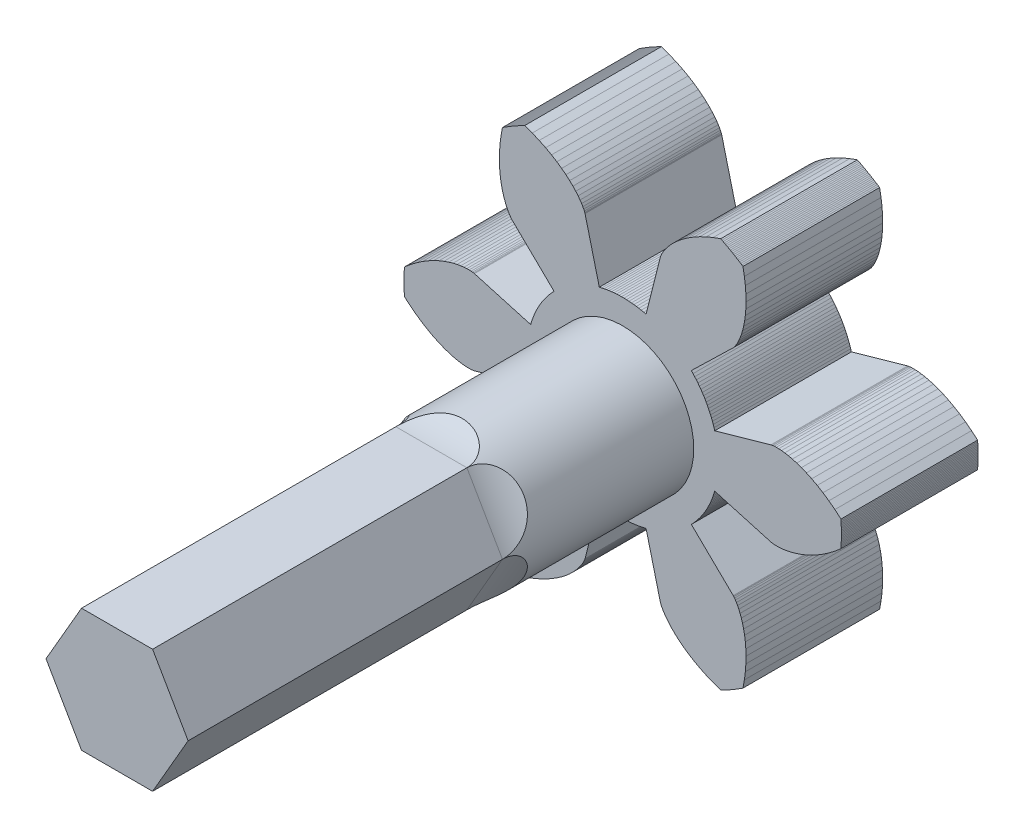
SolidWorks part; units mm, degrees
ref_plane "Front Plane" through (0, 0, 0) normal (0, 0, 1) x (1, 0, 0)
ref_plane "Top Plane" through (0, 0, 0) normal (0, 1, 0) x (1, 0, 0)
ref_plane "Right Plane" through (0, 0, 0) normal (1, 0, 0) x (0, 0, -1)
sketch "Model" plane through (0, 0, 0) normal (0, 0, 1) x (1, 0, 0)
  line L0 (3.3669, -0.9562) -> (5.4237, -1.5403)
  line L1 (5.4237, -1.5403) -> (5.4314, -1.5422)
  line L2 (5.4314, -1.5422) -> (5.4547, -1.5467)
  line L3 (5.4547, -1.5467) -> (5.4938, -1.5524)
  line L4 (5.4938, -1.5524) -> (5.549, -1.5573)
  line L5 (5.549, -1.5573) -> (5.6201, -1.56)
  line L6 (5.6201, -1.56) -> (5.7072, -1.5586)
  line L7 (5.7072, -1.5586) -> (5.8098, -1.5516)
  line L8 (5.8098, -1.5516) -> (5.9276, -1.5373)
  line L9 (5.9276, -1.5373) -> (6.06, -1.514)
  line L10 (6.06, -1.514) -> (6.2065, -1.4801)
  line L11 (6.2065, -1.4801) -> (6.3662, -1.4342)
  line L12 (6.3662, -1.4342) -> (6.5382, -1.3747)
  line L13 (6.5382, -1.3747) -> (6.7214, -1.3003)
  line L14 (6.7214, -1.3003) -> (6.9148, -1.2095)
  line L15 (6.9148, -1.2095) -> (7.1171, -1.1012)
  line L16 (7.1171, -1.1012) -> (7.3268, -0.9741)
  line L17 (7.3268, -0.9741) -> (7.5426, -0.8271)
  line L18 (7.5426, -0.8271) -> (7.763, -0.6594)
  line L19 (7.763, -0.6594) -> (7.9862, -0.47)
  line L20 (7.9862, -0.47) -> (7.9889, -0.4205)
  line L21 (7.9889, -0.4205) -> (7.9914, -0.3711)
  line L22 (7.9914, -0.3711) -> (7.9935, -0.3217)
  line L23 (7.9935, -0.3217) -> (7.9954, -0.2722)
  line L24 (7.9954, -0.2722) -> (7.9969, -0.2227)
  line L25 (7.9969, -0.2227) -> (7.9981, -0.1732)
  line L26 (7.9981, -0.1732) -> (7.999, -0.1237)
  line L27 (7.999, -0.1237) -> (7.9997, -0.0742)
  line L28 (7.9997, -0.0742) -> (8, -0.0247)
  line L29 (8, -0.0247) -> (8, 0.0247)
  line L30 (8, 0.0247) -> (7.9997, 0.0742)
  line L31 (7.9997, 0.0742) -> (7.999, 0.1237)
  line L32 (7.999, 0.1237) -> (7.9981, 0.1732)
  line L33 (7.9981, 0.1732) -> (7.9969, 0.2227)
  line L34 (7.9969, 0.2227) -> (7.9954, 0.2722)
  line L35 (7.9954, 0.2722) -> (7.9935, 0.3217)
  line L36 (7.9935, 0.3217) -> (7.9914, 0.3711)
  line L37 (7.9914, 0.3711) -> (7.9889, 0.4205)
  line L38 (7.9889, 0.4205) -> (7.9862, 0.47)
  line L39 (7.9862, 0.47) -> (7.763, 0.6594)
  line L40 (7.763, 0.6594) -> (7.5426, 0.8271)
  line L41 (7.5426, 0.8271) -> (7.3268, 0.9741)
  line L42 (7.3268, 0.9741) -> (7.1171, 1.1012)
  line L43 (7.1171, 1.1012) -> (6.9148, 1.2095)
  line L44 (6.9148, 1.2095) -> (6.7214, 1.3003)
  line L45 (6.7214, 1.3003) -> (6.5382, 1.3747)
  line L46 (6.5382, 1.3747) -> (6.3662, 1.4342)
  line L47 (6.3662, 1.4342) -> (6.2065, 1.4801)
  line L48 (6.2065, 1.4801) -> (6.06, 1.514)
  line L49 (6.06, 1.514) -> (5.9276, 1.5373)
  line L50 (5.9276, 1.5373) -> (5.8098, 1.5516)
  line L51 (5.8098, 1.5516) -> (5.7072, 1.5586)
  line L52 (5.7072, 1.5586) -> (5.6201, 1.56)
  line L53 (5.6201, 1.56) -> (5.549, 1.5573)
  line L54 (5.549, 1.5573) -> (5.4938, 1.5524)
  line L55 (5.4938, 1.5524) -> (5.4547, 1.5467)
  line L56 (5.4547, 1.5467) -> (5.4314, 1.5422)
  line L57 (5.4314, 1.5422) -> (5.4237, 1.5403)
  line L58 (5.4237, 1.5403) -> (3.3669, 0.9562)
  line L59 (3.3669, 0.9562) -> (3.3409, 1.0433)
  line L60 (3.3409, 1.0433) -> (3.3126, 1.1298)
  line L61 (3.3126, 1.1298) -> (3.2822, 1.2155)
  line L62 (3.2822, 1.2155) -> (3.2495, 1.3004)
  line L63 (3.2495, 1.3004) -> (3.2146, 1.3844)
  line L64 (3.2146, 1.3844) -> (3.1775, 1.4674)
  line L65 (3.1775, 1.4674) -> (3.1383, 1.5495)
  line L66 (3.1383, 1.5495) -> (3.097, 1.6305)
  line L67 (3.097, 1.6305) -> (3.0536, 1.7105)
  line L68 (3.0536, 1.7105) -> (3.0081, 1.7892)
  line L69 (3.0081, 1.7892) -> (2.9606, 1.8668)
  line L70 (2.9606, 1.8668) -> (2.9111, 1.9431)
  line L71 (2.9111, 1.9431) -> (2.8596, 2.0181)
  line L72 (2.8596, 2.0181) -> (2.8062, 2.0917)
  line L73 (2.8062, 2.0917) -> (2.7509, 2.1639)
  line L74 (2.7509, 2.1639) -> (2.6937, 2.2347)
  line L75 (2.6937, 2.2347) -> (2.6347, 2.3039)
  line L76 (2.6347, 2.3039) -> (2.574, 2.3716)
  line L77 (2.574, 2.3716) -> (2.5115, 2.4377)
  line L78 (2.5115, 2.4377) -> (4.0458, 3.9269)
  line L79 (4.0458, 3.9269) -> (4.0512, 3.9326)
  line L80 (4.0512, 3.9326) -> (4.0668, 3.9505)
  line L81 (4.0668, 3.9505) -> (4.0913, 3.9816)
  line L82 (4.0913, 3.9816) -> (4.1232, 4.0269)
  line L83 (4.1232, 4.0269) -> (4.1611, 4.0872)
  line L84 (4.1611, 4.0872) -> (4.2034, 4.1632)
  line L85 (4.2034, 4.1632) -> (4.2486, 4.2556)
  line L86 (4.2486, 4.2556) -> (4.2951, 4.3648)
  line L87 (4.2951, 4.3648) -> (4.3412, 4.4912)
  line L88 (4.3412, 4.4912) -> (4.3851, 4.6349)
  line L89 (4.3851, 4.6349) -> (4.4252, 4.7962)
  line L90 (4.4252, 4.7962) -> (4.4596, 4.9749)
  line L91 (4.4596, 4.9749) -> (4.4868, 5.1708)
  line L92 (4.4868, 5.1708) -> (4.5049, 5.3836)
  line L93 (4.5049, 5.3836) -> (4.5122, 5.613)
  line L94 (4.5122, 5.613) -> (4.507, 5.8582)
  line L95 (4.507, 5.8582) -> (4.4876, 6.1186)
  line L96 (4.4876, 6.1186) -> (4.4525, 6.3932)
  line L97 (4.4525, 6.3932) -> (4.4001, 6.6813)
  line L98 (4.4001, 6.6813) -> (4.3587, 6.7084)
  line L99 (4.3587, 6.7084) -> (4.3171, 6.7352)
  line L100 (4.3171, 6.7352) -> (4.2753, 6.7618)
  line L101 (4.2753, 6.7618) -> (4.2334, 6.7881)
  line L102 (4.2334, 6.7881) -> (4.1913, 6.8142)
  line L103 (4.1913, 6.8142) -> (4.1491, 6.84)
  line L104 (4.1491, 6.84) -> (4.1067, 6.8655)
  line L105 (4.1067, 6.8655) -> (4.0641, 6.8908)
  line L106 (4.0641, 6.8908) -> (4.0214, 6.9158)
  line L107 (4.0214, 6.9158) -> (3.9785, 6.9405)
  line L108 (3.9785, 6.9405) -> (3.9355, 6.965)
  line L109 (3.9355, 6.965) -> (3.8924, 6.9892)
  line L110 (3.8924, 6.9892) -> (3.849, 7.0132)
  line L111 (3.849, 7.0132) -> (3.8056, 7.0369)
  line L112 (3.8056, 7.0369) -> (3.762, 7.0603)
  line L113 (3.762, 7.0603) -> (3.7182, 7.0834)
  line L114 (3.7182, 7.0834) -> (3.6743, 7.1063)
  line L115 (3.6743, 7.1063) -> (3.6303, 7.1289)
  line L116 (3.6303, 7.1289) -> (3.5861, 7.1512)
  line L117 (3.5861, 7.1512) -> (3.3104, 7.0526)
  line L118 (3.3104, 7.0526) -> (3.055, 6.9457)
  line L119 (3.055, 6.9457) -> (2.8199, 6.8322)
  line L120 (2.8199, 6.8322) -> (2.6049, 6.7141)
  line L121 (2.6049, 6.7141) -> (2.4099, 6.5932)
  line L122 (2.4099, 6.5932) -> (2.2346, 6.4711)
  line L123 (2.2346, 6.4711) -> (2.0785, 6.3496)
  line L124 (2.0785, 6.3496) -> (1.941, 6.2304)
  line L125 (1.941, 6.2304) -> (1.8214, 6.1151)
  line L126 (1.8214, 6.1151) -> (1.7189, 6.0051)
  line L127 (1.7189, 6.0051) -> (1.6325, 5.9021)
  line L128 (1.6325, 5.9021) -> (1.5611, 5.8072)
  line L129 (1.5611, 5.8072) -> (1.5038, 5.7219)
  line L130 (1.5038, 5.7219) -> (1.4591, 5.6472)
  line L131 (1.4591, 5.6472) -> (1.4258, 5.5842)
  line L132 (1.4258, 5.5842) -> (1.4025, 5.534)
  line L133 (1.4025, 5.534) -> (1.3878, 5.4972)
  line L134 (1.3878, 5.4972) -> (1.3801, 5.4748)
  line L135 (1.3801, 5.4748) -> (1.3779, 5.4672)
  line L136 (1.3779, 5.4672) -> (0.8554, 3.3939)
  line L137 (0.8554, 3.3939) -> (0.7669, 3.4149)
  line L138 (0.7669, 3.4149) -> (0.6779, 3.4337)
  line L139 (0.6779, 3.4337) -> (0.5884, 3.4502)
  line L140 (0.5884, 3.4502) -> (0.4986, 3.4643)
  line L141 (0.4986, 3.4643) -> (0.4084, 3.4761)
  line L142 (0.4084, 3.4761) -> (0.3179, 3.4855)
  line L143 (0.3179, 3.4855) -> (0.2272, 3.4926)
  line L144 (0.2272, 3.4926) -> (0.1364, 3.4973)
  line L145 (0.1364, 3.4973) -> (0.0455, 3.4997)
  line L146 (0.0455, 3.4997) -> (-0.0455, 3.4997)
  line L147 (-0.0455, 3.4997) -> (-0.1364, 3.4973)
  line L148 (-0.1364, 3.4973) -> (-0.2272, 3.4926)
  line L149 (-0.2272, 3.4926) -> (-0.3179, 3.4855)
  line L150 (-0.3179, 3.4855) -> (-0.4084, 3.4761)
  line L151 (-0.4084, 3.4761) -> (-0.4986, 3.4643)
  line L152 (-0.4986, 3.4643) -> (-0.5884, 3.4502)
  line L153 (-0.5884, 3.4502) -> (-0.6779, 3.4337)
  line L154 (-0.6779, 3.4337) -> (-0.7669, 3.4149)
  line L155 (-0.7669, 3.4149) -> (-0.8554, 3.3939)
  line L156 (-0.8554, 3.3939) -> (-1.3779, 5.4672)
  line L157 (-1.3779, 5.4672) -> (-1.3801, 5.4748)
  line L158 (-1.3801, 5.4748) -> (-1.3878, 5.4972)
  line L159 (-1.3878, 5.4972) -> (-1.4025, 5.534)
  line L160 (-1.4025, 5.534) -> (-1.4258, 5.5842)
  line L161 (-1.4258, 5.5842) -> (-1.4591, 5.6472)
  line L162 (-1.4591, 5.6472) -> (-1.5038, 5.7219)
  line L163 (-1.5038, 5.7219) -> (-1.5611, 5.8072)
  line L164 (-1.5611, 5.8072) -> (-1.6325, 5.9021)
  line L165 (-1.6325, 5.9021) -> (-1.7189, 6.0051)
  line L166 (-1.7189, 6.0051) -> (-1.8214, 6.1151)
  line L167 (-1.8214, 6.1151) -> (-1.941, 6.2304)
  line L168 (-1.941, 6.2304) -> (-2.0785, 6.3496)
  line L169 (-2.0785, 6.3496) -> (-2.2346, 6.4711)
  line L170 (-2.2346, 6.4711) -> (-2.4099, 6.5932)
  line L171 (-2.4099, 6.5932) -> (-2.6049, 6.7141)
  line L172 (-2.6049, 6.7141) -> (-2.8199, 6.8322)
  line L173 (-2.8199, 6.8322) -> (-3.055, 6.9457)
  line L174 (-3.055, 6.9457) -> (-3.3104, 7.0526)
  line L175 (-3.3104, 7.0526) -> (-3.5861, 7.1512)
  line L176 (-3.5861, 7.1512) -> (-3.6303, 7.1289)
  line L177 (-3.6303, 7.1289) -> (-3.6743, 7.1063)
  line L178 (-3.6743, 7.1063) -> (-3.7182, 7.0834)
  line L179 (-3.7182, 7.0834) -> (-3.762, 7.0603)
  line L180 (-3.762, 7.0603) -> (-3.8056, 7.0369)
  line L181 (-3.8056, 7.0369) -> (-3.849, 7.0132)
  line L182 (-3.849, 7.0132) -> (-3.8924, 6.9892)
  line L183 (-3.8924, 6.9892) -> (-3.9355, 6.965)
  line L184 (-3.9355, 6.965) -> (-3.9785, 6.9405)
  line L185 (-3.9785, 6.9405) -> (-4.0214, 6.9158)
  line L186 (-4.0214, 6.9158) -> (-4.0641, 6.8908)
  line L187 (-4.0641, 6.8908) -> (-4.1067, 6.8655)
  line L188 (-4.1067, 6.8655) -> (-4.1491, 6.84)
  line L189 (-4.1491, 6.84) -> (-4.1913, 6.8142)
  line L190 (-4.1913, 6.8142) -> (-4.2334, 6.7881)
  line L191 (-4.2334, 6.7881) -> (-4.2753, 6.7618)
  line L192 (-4.2753, 6.7618) -> (-4.3171, 6.7352)
  line L193 (-4.3171, 6.7352) -> (-4.3587, 6.7084)
  line L194 (-4.3587, 6.7084) -> (-4.4001, 6.6813)
  line L195 (-4.4001, 6.6813) -> (-4.4525, 6.3932)
  line L196 (-4.4525, 6.3932) -> (-4.4876, 6.1186)
  line L197 (-4.4876, 6.1186) -> (-4.507, 5.8582)
  line L198 (-4.507, 5.8582) -> (-4.5122, 5.613)
  line L199 (-4.5122, 5.613) -> (-4.5049, 5.3836)
  line L200 (-4.5049, 5.3836) -> (-4.4868, 5.1708)
  line L201 (-4.4868, 5.1708) -> (-4.4596, 4.9749)
  line L202 (-4.4596, 4.9749) -> (-4.4252, 4.7962)
  line L203 (-4.4252, 4.7962) -> (-4.3851, 4.6349)
  line L204 (-4.3851, 4.6349) -> (-4.3412, 4.4912)
  line L205 (-4.3412, 4.4912) -> (-4.2951, 4.3648)
  line L206 (-4.2951, 4.3648) -> (-4.2486, 4.2556)
  line L207 (-4.2486, 4.2556) -> (-4.2034, 4.1632)
  line L208 (-4.2034, 4.1632) -> (-4.1611, 4.0872)
  line L209 (-4.1611, 4.0872) -> (-4.1232, 4.0269)
  line L210 (-4.1232, 4.0269) -> (-4.0913, 3.9816)
  line L211 (-4.0913, 3.9816) -> (-4.0668, 3.9505)
  line L212 (-4.0668, 3.9505) -> (-4.0512, 3.9326)
  line L213 (-4.0512, 3.9326) -> (-4.0458, 3.9269)
  line L214 (-4.0458, 3.9269) -> (-2.5115, 2.4377)
  line L215 (-2.5115, 2.4377) -> (-2.574, 2.3716)
  line L216 (-2.574, 2.3716) -> (-2.6347, 2.3039)
  line L217 (-2.6347, 2.3039) -> (-2.6937, 2.2347)
  line L218 (-2.6937, 2.2347) -> (-2.7509, 2.1639)
  line L219 (-2.7509, 2.1639) -> (-2.8062, 2.0917)
  line L220 (-2.8062, 2.0917) -> (-2.8596, 2.0181)
  line L221 (-2.8596, 2.0181) -> (-2.9111, 1.9431)
  line L222 (-2.9111, 1.9431) -> (-2.9606, 1.8668)
  line L223 (-2.9606, 1.8668) -> (-3.0081, 1.7892)
  line L224 (-3.0081, 1.7892) -> (-3.0536, 1.7105)
  line L225 (-3.0536, 1.7105) -> (-3.097, 1.6305)
  line L226 (-3.097, 1.6305) -> (-3.1383, 1.5495)
  line L227 (-3.1383, 1.5495) -> (-3.1775, 1.4674)
  line L228 (-3.1775, 1.4674) -> (-3.2146, 1.3844)
  line L229 (-3.2146, 1.3844) -> (-3.2495, 1.3004)
  line L230 (-3.2495, 1.3004) -> (-3.2822, 1.2155)
  line L231 (-3.2822, 1.2155) -> (-3.3126, 1.1298)
  line L232 (-3.3126, 1.1298) -> (-3.3409, 1.0433)
  line L233 (-3.3409, 1.0433) -> (-3.3669, 0.9562)
  line L234 (-3.3669, 0.9562) -> (-5.4237, 1.5403)
  line L235 (-5.4237, 1.5403) -> (-5.4314, 1.5422)
  line L236 (-5.4314, 1.5422) -> (-5.4547, 1.5467)
  line L237 (-5.4547, 1.5467) -> (-5.4938, 1.5524)
  line L238 (-5.4938, 1.5524) -> (-5.549, 1.5573)
  line L239 (-5.549, 1.5573) -> (-5.6201, 1.56)
  line L240 (-5.6201, 1.56) -> (-5.7072, 1.5586)
  line L241 (-5.7072, 1.5586) -> (-5.8098, 1.5516)
  line L242 (-5.8098, 1.5516) -> (-5.9276, 1.5373)
  line L243 (-5.9276, 1.5373) -> (-6.06, 1.514)
  line L244 (-6.06, 1.514) -> (-6.2065, 1.4801)
  line L245 (-6.2065, 1.4801) -> (-6.3662, 1.4342)
  line L246 (-6.3662, 1.4342) -> (-6.5382, 1.3747)
  line L247 (-6.5382, 1.3747) -> (-6.7214, 1.3003)
  line L248 (-6.7214, 1.3003) -> (-6.9148, 1.2095)
  line L249 (-6.9148, 1.2095) -> (-7.1171, 1.1012)
  line L250 (-7.1171, 1.1012) -> (-7.3268, 0.9741)
  line L251 (-7.3268, 0.9741) -> (-7.5426, 0.8271)
  line L252 (-7.5426, 0.8271) -> (-7.763, 0.6594)
  line L253 (-7.763, 0.6594) -> (-7.9862, 0.47)
  line L254 (-7.9862, 0.47) -> (-7.9889, 0.4205)
  line L255 (-7.9889, 0.4205) -> (-7.9914, 0.3711)
  line L256 (-7.9914, 0.3711) -> (-7.9935, 0.3217)
  line L257 (-7.9935, 0.3217) -> (-7.9954, 0.2722)
  line L258 (-7.9954, 0.2722) -> (-7.9969, 0.2227)
  line L259 (-7.9969, 0.2227) -> (-7.9981, 0.1732)
  line L260 (-7.9981, 0.1732) -> (-7.999, 0.1237)
  line L261 (-7.999, 0.1237) -> (-7.9997, 0.0742)
  line L262 (-7.9997, 0.0742) -> (-8, 0.0247)
  line L263 (-8, 0.0247) -> (-8, -0.0247)
  line L264 (-8, -0.0247) -> (-7.9997, -0.0742)
  line L265 (-7.9997, -0.0742) -> (-7.999, -0.1237)
  line L266 (-7.999, -0.1237) -> (-7.9981, -0.1732)
  line L267 (-7.9981, -0.1732) -> (-7.9969, -0.2227)
  line L268 (-7.9969, -0.2227) -> (-7.9954, -0.2722)
  line L269 (-7.9954, -0.2722) -> (-7.9935, -0.3217)
  line L270 (-7.9935, -0.3217) -> (-7.9914, -0.3711)
  line L271 (-7.9914, -0.3711) -> (-7.9889, -0.4205)
  line L272 (-7.9889, -0.4205) -> (-7.9862, -0.47)
  line L273 (-7.9862, -0.47) -> (-7.763, -0.6594)
  line L274 (-7.763, -0.6594) -> (-7.5426, -0.8271)
  line L275 (-7.5426, -0.8271) -> (-7.3268, -0.9741)
  line L276 (-7.3268, -0.9741) -> (-7.1171, -1.1012)
  line L277 (-7.1171, -1.1012) -> (-6.9148, -1.2095)
  line L278 (-6.9148, -1.2095) -> (-6.7214, -1.3003)
  line L279 (-6.7214, -1.3003) -> (-6.5382, -1.3747)
  line L280 (-6.5382, -1.3747) -> (-6.3662, -1.4342)
  line L281 (-6.3662, -1.4342) -> (-6.2065, -1.4801)
  line L282 (-6.2065, -1.4801) -> (-6.06, -1.514)
  line L283 (-6.06, -1.514) -> (-5.9276, -1.5373)
  line L284 (-5.9276, -1.5373) -> (-5.8098, -1.5516)
  line L285 (-5.8098, -1.5516) -> (-5.7072, -1.5586)
  line L286 (-5.7072, -1.5586) -> (-5.6201, -1.56)
  line L287 (-5.6201, -1.56) -> (-5.549, -1.5573)
  line L288 (-5.549, -1.5573) -> (-5.4938, -1.5524)
  line L289 (-5.4938, -1.5524) -> (-5.4547, -1.5467)
  line L290 (-5.4547, -1.5467) -> (-5.4314, -1.5422)
  line L291 (-5.4314, -1.5422) -> (-5.4237, -1.5403)
  line L292 (-5.4237, -1.5403) -> (-3.3669, -0.9562)
  line L293 (-3.3669, -0.9562) -> (-3.3409, -1.0433)
  line L294 (-3.3409, -1.0433) -> (-3.3126, -1.1298)
  line L295 (-3.3126, -1.1298) -> (-3.2822, -1.2155)
  line L296 (-3.2822, -1.2155) -> (-3.2495, -1.3004)
  line L297 (-3.2495, -1.3004) -> (-3.2146, -1.3844)
  line L298 (-3.2146, -1.3844) -> (-3.1775, -1.4674)
  line L299 (-3.1775, -1.4674) -> (-3.1383, -1.5495)
  line L300 (-3.1383, -1.5495) -> (-3.097, -1.6305)
  line L301 (-3.097, -1.6305) -> (-3.0536, -1.7105)
  line L302 (-3.0536, -1.7105) -> (-3.0081, -1.7892)
  line L303 (-3.0081, -1.7892) -> (-2.9606, -1.8668)
  line L304 (-2.9606, -1.8668) -> (-2.9111, -1.9431)
  line L305 (-2.9111, -1.9431) -> (-2.8596, -2.0181)
  line L306 (-2.8596, -2.0181) -> (-2.8062, -2.0917)
  line L307 (-2.8062, -2.0917) -> (-2.7509, -2.1639)
  line L308 (-2.7509, -2.1639) -> (-2.6937, -2.2347)
  line L309 (-2.6937, -2.2347) -> (-2.6347, -2.3039)
  line L310 (-2.6347, -2.3039) -> (-2.574, -2.3716)
  line L311 (-2.574, -2.3716) -> (-2.5115, -2.4377)
  line L312 (-2.5115, -2.4377) -> (-4.0458, -3.9269)
  line L313 (-4.0458, -3.9269) -> (-4.0512, -3.9326)
  line L314 (-4.0512, -3.9326) -> (-4.0668, -3.9505)
  line L315 (-4.0668, -3.9505) -> (-4.0913, -3.9816)
  line L316 (-4.0913, -3.9816) -> (-4.1232, -4.0269)
  line L317 (-4.1232, -4.0269) -> (-4.1611, -4.0872)
  line L318 (-4.1611, -4.0872) -> (-4.2034, -4.1632)
  line L319 (-4.2034, -4.1632) -> (-4.2486, -4.2556)
  line L320 (-4.2486, -4.2556) -> (-4.2951, -4.3648)
  line L321 (-4.2951, -4.3648) -> (-4.3412, -4.4912)
  line L322 (-4.3412, -4.4912) -> (-4.3851, -4.6349)
  line L323 (-4.3851, -4.6349) -> (-4.4252, -4.7962)
  line L324 (-4.4252, -4.7962) -> (-4.4596, -4.9749)
  line L325 (-4.4596, -4.9749) -> (-4.4868, -5.1708)
  line L326 (-4.4868, -5.1708) -> (-4.5049, -5.3836)
  line L327 (-4.5049, -5.3836) -> (-4.5122, -5.613)
  line L328 (-4.5122, -5.613) -> (-4.507, -5.8582)
  line L329 (-4.507, -5.8582) -> (-4.4876, -6.1186)
  line L330 (-4.4876, -6.1186) -> (-4.4525, -6.3932)
  line L331 (-4.4525, -6.3932) -> (-4.4001, -6.6813)
  line L332 (-4.4001, -6.6813) -> (-4.3587, -6.7084)
  line L333 (-4.3587, -6.7084) -> (-4.3171, -6.7352)
  line L334 (-4.3171, -6.7352) -> (-4.2753, -6.7618)
  line L335 (-4.2753, -6.7618) -> (-4.2334, -6.7881)
  line L336 (-4.2334, -6.7881) -> (-4.1913, -6.8142)
  line L337 (-4.1913, -6.8142) -> (-4.1491, -6.84)
  line L338 (-4.1491, -6.84) -> (-4.1067, -6.8655)
  line L339 (-4.1067, -6.8655) -> (-4.0641, -6.8908)
  line L340 (-4.0641, -6.8908) -> (-4.0214, -6.9158)
  line L341 (-4.0214, -6.9158) -> (-3.9785, -6.9405)
  line L342 (-3.9785, -6.9405) -> (-3.9355, -6.965)
  line L343 (-3.9355, -6.965) -> (-3.8924, -6.9892)
  line L344 (-3.8924, -6.9892) -> (-3.849, -7.0132)
  line L345 (-3.849, -7.0132) -> (-3.8056, -7.0369)
  line L346 (-3.8056, -7.0369) -> (-3.762, -7.0603)
  line L347 (-3.762, -7.0603) -> (-3.7182, -7.0834)
  line L348 (-3.7182, -7.0834) -> (-3.6743, -7.1063)
  line L349 (-3.6743, -7.1063) -> (-3.6303, -7.1289)
  line L350 (-3.6303, -7.1289) -> (-3.5861, -7.1512)
  line L351 (-3.5861, -7.1512) -> (-3.3104, -7.0526)
  line L352 (-3.3104, -7.0526) -> (-3.055, -6.9457)
  line L353 (-3.055, -6.9457) -> (-2.8199, -6.8322)
  line L354 (-2.8199, -6.8322) -> (-2.6049, -6.7141)
  line L355 (-2.6049, -6.7141) -> (-2.4099, -6.5932)
  line L356 (-2.4099, -6.5932) -> (-2.2346, -6.4711)
  line L357 (-2.2346, -6.4711) -> (-2.0785, -6.3496)
  line L358 (-2.0785, -6.3496) -> (-1.941, -6.2304)
  line L359 (-1.941, -6.2304) -> (-1.8214, -6.1151)
  line L360 (-1.8214, -6.1151) -> (-1.7189, -6.0051)
  line L361 (-1.7189, -6.0051) -> (-1.6325, -5.9021)
  line L362 (-1.6325, -5.9021) -> (-1.5611, -5.8072)
  line L363 (-1.5611, -5.8072) -> (-1.5038, -5.7219)
  line L364 (-1.5038, -5.7219) -> (-1.4591, -5.6472)
  line L365 (-1.4591, -5.6472) -> (-1.4258, -5.5842)
  line L366 (-1.4258, -5.5842) -> (-1.4025, -5.534)
  line L367 (-1.4025, -5.534) -> (-1.3878, -5.4972)
  line L368 (-1.3878, -5.4972) -> (-1.3801, -5.4748)
  line L369 (-1.3801, -5.4748) -> (-1.3779, -5.4672)
  line L370 (-1.3779, -5.4672) -> (-0.8554, -3.3939)
  line L371 (-0.8554, -3.3939) -> (-0.7669, -3.4149)
  line L372 (-0.7669, -3.4149) -> (-0.6779, -3.4337)
  line L373 (-0.6779, -3.4337) -> (-0.5884, -3.4502)
  line L374 (-0.5884, -3.4502) -> (-0.4986, -3.4643)
  line L375 (-0.4986, -3.4643) -> (-0.4084, -3.4761)
  line L376 (-0.4084, -3.4761) -> (-0.3179, -3.4855)
  line L377 (-0.3179, -3.4855) -> (-0.2272, -3.4926)
  line L378 (-0.2272, -3.4926) -> (-0.1364, -3.4973)
  line L379 (-0.1364, -3.4973) -> (-0.0455, -3.4997)
  line L380 (-0.0455, -3.4997) -> (0.0455, -3.4997)
  line L381 (0.0455, -3.4997) -> (0.1364, -3.4973)
  line L382 (0.1364, -3.4973) -> (0.2272, -3.4926)
  line L383 (0.2272, -3.4926) -> (0.3179, -3.4855)
  line L384 (0.3179, -3.4855) -> (0.4084, -3.4761)
  line L385 (0.4084, -3.4761) -> (0.4986, -3.4643)
  line L386 (0.4986, -3.4643) -> (0.5884, -3.4502)
  line L387 (0.5884, -3.4502) -> (0.6779, -3.4337)
  line L388 (0.6779, -3.4337) -> (0.7669, -3.4149)
  line L389 (0.7669, -3.4149) -> (0.8554, -3.3939)
  line L390 (0.8554, -3.3939) -> (1.3779, -5.4672)
  line L391 (1.3779, -5.4672) -> (1.3801, -5.4748)
  line L392 (1.3801, -5.4748) -> (1.3878, -5.4972)
  line L393 (1.3878, -5.4972) -> (1.4025, -5.534)
  line L394 (1.4025, -5.534) -> (1.4258, -5.5842)
  line L395 (1.4258, -5.5842) -> (1.4591, -5.6472)
  line L396 (1.4591, -5.6472) -> (1.5038, -5.7219)
  line L397 (1.5038, -5.7219) -> (1.5611, -5.8072)
  line L398 (1.5611, -5.8072) -> (1.6325, -5.9021)
  line L399 (1.6325, -5.9021) -> (1.7189, -6.0051)
  line L400 (1.7189, -6.0051) -> (1.8214, -6.1151)
  line L401 (1.8214, -6.1151) -> (1.941, -6.2304)
  line L402 (1.941, -6.2304) -> (2.0785, -6.3496)
  line L403 (2.0785, -6.3496) -> (2.2346, -6.4711)
  line L404 (2.2346, -6.4711) -> (2.4099, -6.5932)
  line L405 (2.4099, -6.5932) -> (2.6049, -6.7141)
  line L406 (2.6049, -6.7141) -> (2.8199, -6.8322)
  line L407 (2.8199, -6.8322) -> (3.055, -6.9457)
  line L408 (3.055, -6.9457) -> (3.3104, -7.0526)
  line L409 (3.3104, -7.0526) -> (3.5861, -7.1512)
  line L410 (3.5861, -7.1512) -> (3.6303, -7.1289)
  line L411 (3.6303, -7.1289) -> (3.6743, -7.1063)
  line L412 (3.6743, -7.1063) -> (3.7182, -7.0834)
  line L413 (3.7182, -7.0834) -> (3.762, -7.0603)
  line L414 (3.762, -7.0603) -> (3.8056, -7.0369)
  line L415 (3.8056, -7.0369) -> (3.849, -7.0132)
  line L416 (3.849, -7.0132) -> (3.8924, -6.9892)
  line L417 (3.8924, -6.9892) -> (3.9355, -6.965)
  line L418 (3.9355, -6.965) -> (3.9785, -6.9405)
  line L419 (3.9785, -6.9405) -> (4.0214, -6.9158)
  line L420 (4.0214, -6.9158) -> (4.0641, -6.8908)
  line L421 (4.0641, -6.8908) -> (4.1067, -6.8655)
  line L422 (4.1067, -6.8655) -> (4.1491, -6.84)
  line L423 (4.1491, -6.84) -> (4.1913, -6.8142)
  line L424 (4.1913, -6.8142) -> (4.2334, -6.7881)
  line L425 (4.2334, -6.7881) -> (4.2753, -6.7618)
  line L426 (4.2753, -6.7618) -> (4.3171, -6.7352)
  line L427 (4.3171, -6.7352) -> (4.3587, -6.7084)
  line L428 (4.3587, -6.7084) -> (4.4001, -6.6813)
  line L429 (4.4001, -6.6813) -> (4.4525, -6.3932)
  line L430 (4.4525, -6.3932) -> (4.4876, -6.1186)
  line L431 (4.4876, -6.1186) -> (4.507, -5.8582)
  line L432 (4.507, -5.8582) -> (4.5122, -5.613)
  line L433 (4.5122, -5.613) -> (4.5049, -5.3836)
  line L434 (4.5049, -5.3836) -> (4.4868, -5.1708)
  line L435 (4.4868, -5.1708) -> (4.4596, -4.9749)
  line L436 (4.4596, -4.9749) -> (4.4252, -4.7962)
  line L437 (4.4252, -4.7962) -> (4.3851, -4.6349)
  line L438 (4.3851, -4.6349) -> (4.3412, -4.4912)
  line L439 (4.3412, -4.4912) -> (4.2951, -4.3648)
  line L440 (4.2951, -4.3648) -> (4.2486, -4.2556)
  line L441 (4.2486, -4.2556) -> (4.2034, -4.1632)
  line L442 (4.2034, -4.1632) -> (4.1611, -4.0872)
  line L443 (4.1611, -4.0872) -> (4.1232, -4.0269)
  line L444 (4.1232, -4.0269) -> (4.0913, -3.9816)
  line L445 (4.0913, -3.9816) -> (4.0668, -3.9505)
  line L446 (4.0668, -3.9505) -> (4.0512, -3.9326)
  line L447 (4.0512, -3.9326) -> (4.0458, -3.9269)
  line L448 (4.0458, -3.9269) -> (2.5115, -2.4377)
  line L449 (2.5115, -2.4377) -> (2.574, -2.3716)
  line L450 (2.574, -2.3716) -> (2.6347, -2.3039)
  line L451 (2.6347, -2.3039) -> (2.6937, -2.2347)
  line L452 (2.6937, -2.2347) -> (2.7509, -2.1639)
  line L453 (2.7509, -2.1639) -> (2.8062, -2.0917)
  line L454 (2.8062, -2.0917) -> (2.8596, -2.0181)
  line L455 (2.8596, -2.0181) -> (2.9111, -1.9431)
  line L456 (2.9111, -1.9431) -> (2.9606, -1.8668)
  line L457 (2.9606, -1.8668) -> (3.0081, -1.7892)
  line L458 (3.0081, -1.7892) -> (3.0536, -1.7105)
  line L459 (3.0536, -1.7105) -> (3.097, -1.6305)
  line L460 (3.097, -1.6305) -> (3.1383, -1.5495)
  line L461 (3.1383, -1.5495) -> (3.1775, -1.4674)
  line L462 (3.1775, -1.4674) -> (3.2146, -1.3844)
  line L463 (3.2146, -1.3844) -> (3.2495, -1.3004)
  line L464 (3.2495, -1.3004) -> (3.2822, -1.2155)
  line L465 (3.2822, -1.2155) -> (3.3126, -1.1298)
  line L466 (3.3126, -1.1298) -> (3.3409, -1.0433)
  line L467 (3.3409, -1.0433) -> (3.3669, -0.9562)
  circle A0 centre (0, 0) radius 2.6
extrude "Boss-Extrude1" add sketch "Model" along normal blind 5
extrude "Boss-Extrude2" add sketch "Model<2>" along normal blind 23.5 contours A0 region at (0, 0, 0)
sketch "Model<2>" plane through (0, 0, 0) normal (0, 0, 1) x (1, 0, 0) same geometry as "Model"
sketch "Sketch1" plane through (0, 0, 5) normal (0, 0, 1) x (1, 0, 0)
  line L1 (2.6, 0) -> (1.3, 2.2517)
  line L2 (1.3, 2.2517) -> (-1.3, 2.2517)
  line L3 (-1.3, 2.2517) -> (-2.6, 0)
  line L4 (-2.6, 0) -> (-1.3, -2.2517)
  line L5 (-1.3, -2.2517) -> (1.3, -2.2517)
  line L6 (1.3, -2.2517) -> (2.6, 0)
  circle A0 centre (0, 0) radius 2.2517 construction
  circle A1 centre (0, 0) radius 2.6
extrude "Cut-Extrude1" cut sketch "Sketch1" along normal up to next from offset 5 contours L4 A1 | L5 A1 | L6 A1 | L1 A1 | L3 A1 | L2 A1 region at (2.0714, -1.1959, 5) region at (2.0714, 1.1959, 5) region at (0, 2.3918, 5) region at (0, -2.3918, 5) region at (-2.0714, 1.1959, 5) region at (-2.0714, -1.1959, 5)
fillet "Fillet2" radius 2 3 edges at (0, 2.2517, 10) (-1.95, -1.1258, 10) (1.95, -1.1258, 10)
fillet "Fillet3" radius 2 3 edges at (1.95, 1.1258, 10) (0, -2.2517, 10) (-1.95, 1.1258, 10)
